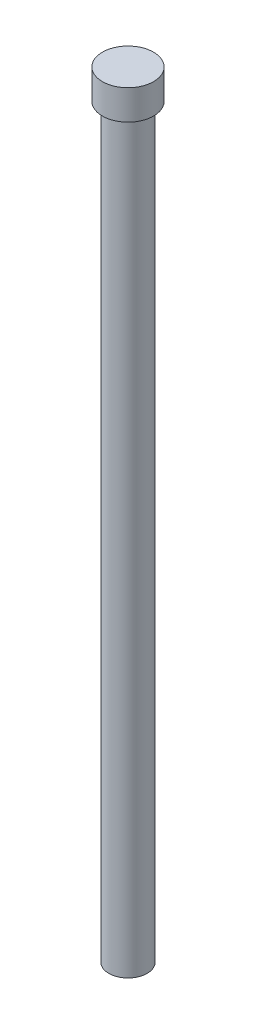
SolidWorks part; units mm, degrees
ref_plane "Front Plane" through (0, 0, 0) normal (0, 0, 1) x (1, 0, 0)
ref_plane "Top Plane" through (0, 0, 0) normal (0, 1, 0) x (1, 0, 0)
ref_plane "Right Plane" through (0, 0, 0) normal (1, 0, 0) x (0, 0, -1)
sketch "Sketch1" plane through (0, 0, 0) normal (0, 1, 0) x (1, 0, 0)
  circle A0 centre (0, 0) radius 0.9
  dimension "D1" = 1.8
extrude "Boss-Extrude1" add sketch "Sketch1" along normal blind 35
sketch "Sketch2" plane through (0, 35, 0) normal (0, 1, 0) x (1, 0, 0)
  circle A0 centre (0, 0) radius 1.2
  dimension "D1" = 2.4
extrude "Boss-Extrude2" add sketch "Sketch2" along normal blind 1.4
